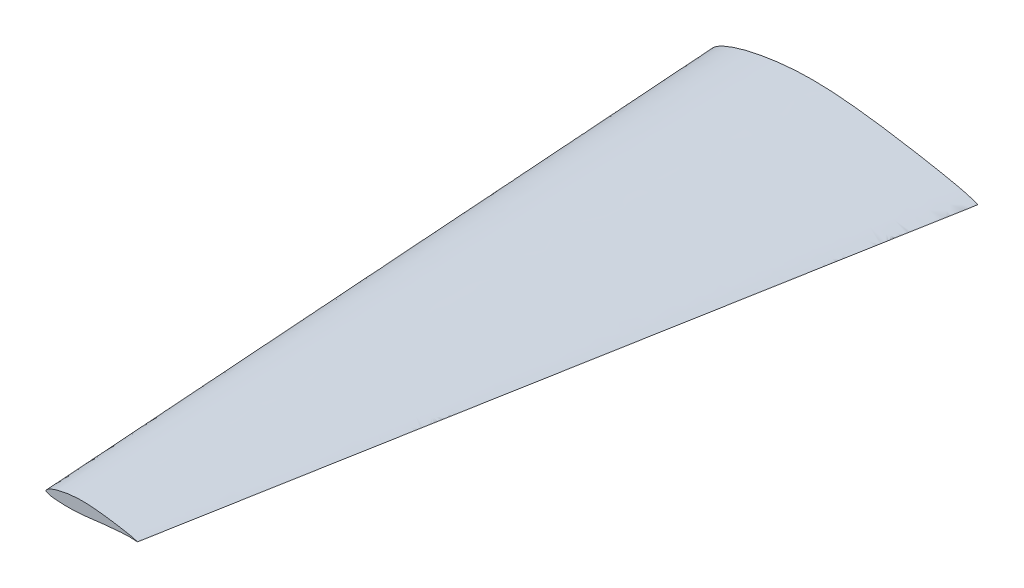
SolidWorks part; units mm, degrees
ref_plane "Front Plane" through (0, 0, 0) normal (0, 0, 1) x (1, 0, 0)
ref_plane "Top Plane" through (0, 0, 0) normal (0, 1, 0) x (1, 0, 0)
ref_plane "Right Plane" through (0, 0, 0) normal (1, 0, 0) x (0, 0, -1)
curve "Curve1"
  spline degree 3 poles (0.9921, 0.0008, 0) (1.0019, -0.0008, 0) (0.9929, 0.0016, 0) (0.9861, 0.0043, 0) (0.9706, 0.0096, 0) (0.9519, 0.0152, 0) (0.9278, 0.021, 0) (0.8992, 0.0273, 0) (0.8662, 0.0341, 0) (0.8293, 0.0413, 0) (0.789, 0.0488, 0) (0.746, 0.0564, 0) (0.7007, 0.0641, 0) (0.6538, 0.0714, 0) (0.6058, 0.0784, 0) (0.5573, 0.0846, 0) (0.5088, 0.0898, 0) (0.4609, 0.0938, 0) (0.4138, 0.0961, 0) (0.3679, 0.0966, 0) (0.3232, 0.0952, 0) (0.2801, 0.092, 0) (0.2388, 0.0874, 0) (0.1997, 0.0815, 0) (0.1631, 0.0746, 0) (0.1296, 0.0669, 0) (0.0993, 0.0585, 0) (0.0726, 0.0496, 0) (0.0499, 0.0404, 0) (0.0312, 0.031, 0) (0.0168, 0.0217, 0) (0.0085, 0.0145, 0) (0.0039, 0.009, 0) (0.0018, 0.0058, 0) (0.0004, 0.0024, 0) (0, 0.0003, 0) (0, -0.0012, 0) (0.0006, -0.0026, 0) (0.002, -0.0043, 0) (0.0049, -0.007, 0) (0.0107, -0.0108, 0) (0.0215, -0.0156, 0) (0.0378, -0.0206, 0) (0.0598, -0.0253, 0) (0.0864, -0.0294, 0) (0.1174, -0.033, 0) (0.1523, -0.036, 0) (0.1908, -0.0383, 0) (0.2323, -0.0397, 0) (0.2764, -0.0402, 0) (0.3228, -0.0395, 0) (0.3711, -0.0373, 0) (0.4212, -0.0335, 0) (0.4729, -0.0284, 0) (0.526, -0.0227, 0) (0.5798, -0.0169, 0) (0.6336, -0.0114, 0) (0.6866, -0.0064, 0) (0.7378, -0.0023, 0) (0.7866, 0.0009, 0) (0.832, 0.0031, 0) (0.8733, 0.0042, 0) (0.9096, 0.0045, 0) (0.9406, 0.0038, 0) (0.9645, 0.0029, 0) (0.984, 0.0013, 0) (0.9921, 0.0008, 0) (1.0019, -0.0008, 0) (0.9929, 0.0016, 0) knots -0.016161 -0.007282 -0.001839 0 0.00178 0.006777 0.014308 0.024046 0.036116 0.050547 0.06713 0.085624 0.105767 0.127282 0.149864 0.17323 0.197069 0.221103 0.245052 0.268663 0.291773 0.314299 0.336178 0.357377 0.377792 0.397225 0.415489 0.432417 0.447849 0.461651 0.473687 0.483898 0.492263 0.498797 0.499955 0.502811 0.504371 0.50536 0.505925 0.506503 0.507535 0.509205 0.512345 0.517665 0.526422 0.537425 0.550643 0.565966 0.583206 0.602155 0.622587 0.644255 0.666998 0.690703 0.715307 0.740824 0.767084 0.793717 0.820331 0.846519 0.871863 0.895937 0.918335 0.938667 0.956573 0.971715 0.983839 0.992718 0.998161 1 1.00178 1.006777 1.014308 periodic
sketch "Sketch1" plane through (0, 0, 0) normal (0, 0, 1) x (1, 0, 0)
  line L0 (1167.2059, -30.8288) -> (-1162.7941, -35.0845) construction
  spline S1 degree 3 poles (1148.7784, -27.977) (1171.7172, -31.8039) (1150.5581, -26.2223) (1134.8254, -19.9356) (1098.6121, -7.5831) (1055.1085, 5.302) (998.7633, 18.7181) (932.1355, 33.1472) (855.1368, 48.7571) (769.1604, 65.315) (675.3297, 82.539) (574.9855, 100.1298) (469.4321, 117.5896) (360.0593, 134.5108) (248.1955, 150.3414) (135.1701, 164.471) (22.251, 176.387) (-89.4773, 185.3614) (-199.1981, 190.448) (-306.2906, 191.3607) (-410.3035, 187.861) (-510.7288, 180.1745) (-606.9241, 169.0794) (-698.0601, 155.2587) (-783.1654, 138.9679) (-861.372, 120.7249) (-931.8769, 100.9237) (-993.9265, 80.0009) (-1046.9152, 58.4337) (-1090.3321, 36.5318) (-1123.8027, 14.8406) (-1143.0848, -2.0984) (-1153.7633, -14.9763) (-1158.687, -22.3942) (-1162.0098, -30.347) (-1162.9632, -35.2319) (-1162.7814, -38.6558) (-1161.4072, -41.8761) (-1158.1965, -46.0146) (-1151.3491, -52.3048) (-1137.7712, -61.0453) (-1112.7076, -72.0855) (-1074.5686, -83.6296) (-1023.3774, -94.5176) (-961.3579, -103.9657) (-889.2059, -112.1487) (-807.7812, -118.8643) (-718.123, -123.9211) (-621.353, -127.1211) (-518.5136, -128.0007) (-410.4966, -125.9274) (-297.9318, -120.4997) (-181.1922, -111.4131) (-60.6773, -99.1751) (62.927, -85.6192) (188.2527, -71.7896) (313.5351, -58.6199) (436.8922, -46.706) (556.3778, -36.7171) (670.0141, -28.9741) (775.8051, -23.5992) (871.9959, -20.7419) (956.4498, -19.9967) (1028.6755, -21.2748) (1084.3745, -23.2358) (1129.9205, -26.8607) (1148.7784, -27.977) (1171.7172, -31.8039) (1150.5581, -26.2223) knots -0.016161 -0.007282 -0.001839 0 0.00178 0.006777 0.014308 0.024046 0.036116 0.050547 0.06713 0.085624 0.105767 0.127282 0.149864 0.17323 0.197069 0.221103 0.245052 0.268663 0.291773 0.314299 0.336178 0.357377 0.377792 0.397225 0.415489 0.432417 0.447849 0.461651 0.473687 0.483898 0.492263 0.498797 0.499955 0.502811 0.504371 0.50536 0.505925 0.506503 0.507535 0.509205 0.512345 0.517665 0.526422 0.537425 0.550643 0.565966 0.583206 0.602155 0.622587 0.644255 0.666998 0.690703 0.715307 0.740824 0.767084 0.793717 0.820331 0.846519 0.871863 0.895937 0.918335 0.938667 0.956573 0.971715 0.983839 0.992718 0.998161 1 1.00178 1.006777 1.014308 only from (1167.2059, -30.8288) to (1167.2059, -30.8288)
  dimension "D1" = 2330
ref_plane "Plane1" through (0, 0, 6200) normal (0, 0, 1) x (1, 0, 0)
ref_plane "Plane3" through (0, -35.0845, 0) normal (0, 1, 0) x (1, 0, 0)
sketch "Sketch4" plane through (0, -35.0845, 0) normal (0, 1, 0) x (1, 0, 0)
  line L1 (1167.2059, 0) -> (-1162.7941, 0) construction
  line L2 (-172.1886, -6200) -> (172.1886, -6200) construction
  line L4 (-1162.7941, 0) -> (-862.7941, -6200)
sketch "Sketch5" plane through (0, 0, 6200) normal (0, 0, 1) x (1, 0, 0)
  line L0 (46.251, -35.2354) -> (-753.7688, -35.3009) construction
  spline S1 degree 3 poles (39.9103, -34.3504) (47.78, -35.5469) (40.5107, -33.741) (35.0952, -31.6671) (22.6402, -27.6181) (7.6874, -23.4229) (-11.663, -19.1093) (-34.5377, -14.4998) (-60.9677, -9.5373) (-90.4749, -4.2947) (-122.6736, 1.1372) (-157.1033, 6.6624) (-193.3153, 12.1171) (-230.8318, 17.3686) (-269.1955, 22.2345) (-307.9483, 26.5125) (-346.6538, 30.0335) (-384.9373, 32.5536) (-422.5145, 33.7529) (-459.1715, 33.5367) (-494.7528, 31.8256) (-529.0855, 28.6992) (-561.9538, 24.4271) (-593.0769, 19.2472) (-622.124, 13.2516) (-648.8002, 6.6219) (-672.8329, -0.5031) (-693.9662, -7.9701) (-711.9952, -15.6131) (-726.7466, -23.3233) (-738.0949, -30.9123) (-744.6106, -36.8049) (-748.2018, -41.2651) (-749.8503, -43.8282) (-750.9483, -46.5664) (-751.2505, -48.243) (-751.1714, -49.4139) (-750.6851, -50.5093) (-749.5659, -51.9099) (-747.1913, -54.0289) (-742.5011, -56.9533) (-733.8685, -60.6082) (-720.7584, -64.3709) (-703.1844, -67.8447) (-681.9116, -70.7722) (-657.1771, -73.2167) (-629.2762, -75.1133) (-598.5656, -76.4015) (-565.4302, -77.0191) (-530.2289, -76.8125) (-493.2702, -75.5698) (-454.7715, -73.1566) (-414.8621, -69.4706) (-373.6761, -64.6873) (-331.4393, -59.4377) (-288.6147, -54.086) (-245.8016, -48.9603) (-203.6413, -44.2739) (-162.7964, -40.2655) (-123.9425, -37.0546) (-87.7619, -34.6929) (-54.8546, -33.2402) (-25.9538, -32.5684) (-1.2281, -32.6493) (17.8446, -33.0456) (33.4506, -34.0614) (39.9103, -34.3504) (47.78, -35.5469) (40.5107, -33.741) knots -0.016161 -0.007282 -0.001839 0 0.00178 0.006777 0.014308 0.024046 0.036116 0.050547 0.06713 0.085624 0.105767 0.127282 0.149864 0.17323 0.197069 0.221103 0.245052 0.268663 0.291773 0.314299 0.336178 0.357377 0.377792 0.397225 0.415489 0.432417 0.447849 0.461651 0.473687 0.483898 0.492263 0.498797 0.499955 0.502811 0.504371 0.50536 0.505925 0.506503 0.507535 0.509205 0.512345 0.517665 0.526422 0.537425 0.550643 0.565966 0.583206 0.602155 0.622587 0.644255 0.666998 0.690703 0.715307 0.740824 0.767084 0.793717 0.820331 0.846519 0.871863 0.895937 0.918335 0.938667 0.956573 0.971715 0.983839 0.992718 0.998161 1 1.00178 1.006777 1.014308 only from (46.2312, -35.2354) to (46.2312, -35.2354)
  dimension "D1" = 800
sketch "Sketch6" plane through (0, 0, 6200) normal (0, 0, 1) x (1, 0, 0)
  line L0 (-753.7688, -35.3009) -> (-751.2083, -48.6103)
  spline S0 degree 3 poles (39.9103, -34.3504) (47.78, -35.5469) (40.5107, -33.741) (35.0952, -31.6671) (22.6402, -27.6181) (7.6874, -23.4229) (-11.663, -19.1093) (-34.5377, -14.4998) (-60.9677, -9.5373) (-90.4749, -4.2947) (-122.6736, 1.1372) (-157.1033, 6.6624) (-193.3153, 12.1171) (-230.8318, 17.3686) (-269.1955, 22.2345) (-307.9483, 26.5125) (-346.6538, 30.0335) (-384.9373, 32.5536) (-422.5145, 33.7529) (-459.1715, 33.5367) (-494.7528, 31.8256) (-529.0855, 28.6992) (-561.9538, 24.4271) (-593.0769, 19.2472) (-622.124, 13.2516) (-648.8002, 6.6219) (-672.8329, -0.5031) (-693.9662, -7.9701) (-711.9952, -15.6131) (-726.7466, -23.3233) (-738.0949, -30.9123) (-744.6106, -36.8049) (-748.2018, -41.2651) (-749.8503, -43.8282) (-750.9483, -46.5664) (-751.2505, -48.243) (-751.1714, -49.4139) (-750.6851, -50.5093) (-749.5659, -51.9099) (-747.1913, -54.0289) (-742.5011, -56.9533) (-733.8685, -60.6082) (-720.7584, -64.3709) (-703.1844, -67.8447) (-681.9116, -70.7722) (-657.1771, -73.2167) (-629.2762, -75.1133) (-598.5656, -76.4015) (-565.4302, -77.0191) (-530.2289, -76.8125) (-493.2702, -75.5698) (-454.7715, -73.1566) (-414.8621, -69.4706) (-373.6761, -64.6873) (-331.4393, -59.4377) (-288.6147, -54.086) (-245.8016, -48.9603) (-203.6413, -44.2739) (-162.7964, -40.2655) (-123.9425, -37.0546) (-87.7619, -34.6929) (-54.8546, -33.2402) (-25.9538, -32.5684) (-1.2281, -32.6493) (17.8446, -33.0456) (33.4506, -34.0614) (39.9103, -34.3504) (47.78, -35.5469) (40.5107, -33.741) knots -0.016161 -0.007282 -0.001839 0 0.00178 0.006777 0.014308 0.024046 0.036116 0.050547 0.06713 0.085624 0.105767 0.127282 0.149864 0.17323 0.197069 0.221103 0.245052 0.268663 0.291773 0.314299 0.336178 0.357377 0.377792 0.397225 0.415489 0.432417 0.447849 0.461651 0.473687 0.483898 0.492263 0.498797 0.499955 0.502811 0.504371 0.50536 0.505925 0.506503 0.507535 0.509205 0.512345 0.517665 0.526422 0.537425 0.550643 0.565966 0.583206 0.602155 0.622587 0.644255 0.666998 0.690703 0.715307 0.740824 0.767084 0.793717 0.820331 0.846519 0.871863 0.895937 0.918335 0.938667 0.956573 0.971715 0.983839 0.992718 0.998161 1 1.00178 1.006777 1.014308 only from (46.2312, -35.2354) to (46.2312, -35.2354) construction
ref_axis "Axis2" through (-751.2083, -48.6103, 6200) along (-0.0662, 0.0022, -0.9978)
loft "Loft5" add profiles "Sketch1", "Sketch5" connector at (-1162.8009, -35.1632, 0) connector at (-751.1274, -47.6465, 6200)
sketch "Sketch7" plane through (0, 0, 0) normal (0, 0, -1) x (-1, 0, 0)
  line L1 (378.6621, 100.8715) -> (605.0337, 100.8715)
  line L2 (378.6621, 100.8715) -> (378.6621, -50.9306)
  line L3 (378.6621, -50.9306) -> (605.0337, -50.9306)
  line L4 (605.0337, 100.8715) -> (605.0337, -50.9306)
extrude "Boss-Extrude1" add sketch "Sketch7" along normal blind 10
